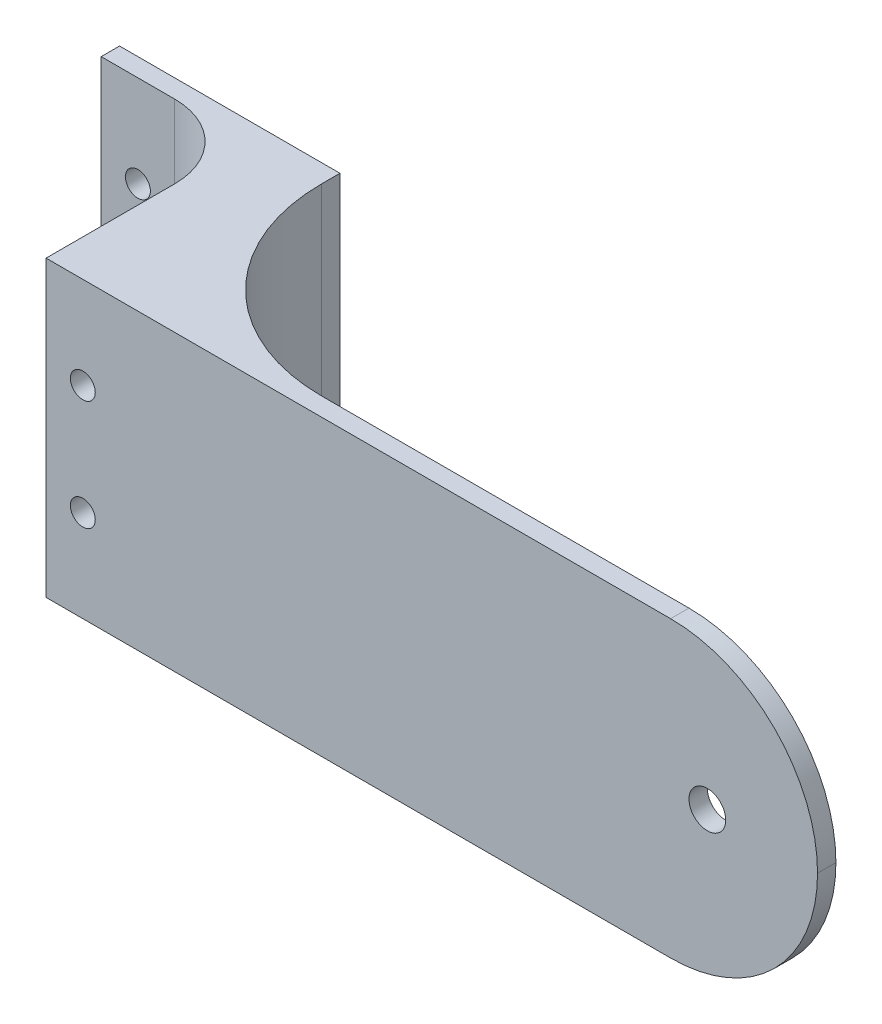
SolidWorks part; units mm, degrees
material "6061-T6 (SS)"
ref_plane "Front Plane" through (0, 0, 0) normal (0, 0, 1) x (1, 0, 0)
ref_plane "Top Plane" through (0, 0, 0) normal (0, 1, 0) x (1, 0, 0)
ref_plane "Right Plane" through (0, 0, 0) normal (1, 0, 0) x (0, 0, -1)
ref_plane "Plane1" through (0, 0, 15.875) normal (0, 0, 1) x (1, 0, 0)
sketch "Sketch1" plane through (0, 0, 15.875) normal (0, 0, 1) x (1, 0, 0)
  line L0 (0, -25.4) -> (0, 25.4) construction
  line L1 (0, 25.4) -> (-38.1, 25.4) construction
  line L2 (-38.1, 25.4) -> (-38.1, -25.4)
  line L3 (-38.1, -25.4) -> (-25.4, -25.4)
  line L5 (0, 25.4) -> (-38.1, 25.4)
  line L6 (-25.4, -25.4) -> (0, -25.4)
  line L7 (0, -25.4) -> (0, 25.4)
  point P2 (0, 0)
  dimension "D1" = 50.8
  dimension "D2" = 38.1
  dimension "D3" = 12.7
extrude "Boss-Extrude1" add sketch "Sketch1" along normal blind 3.175
ref_plane "Plane2" through (0, 0, 50.8) normal (0, 0, 1) x (1, 0, 0)
sketch "Sketch2" plane through (0, 0, 50.8) normal (0, 0, 1) x (1, 0, 0)
  line L0 (0, -25.4) -> (0, 25.4) construction
  line L1 (0, 25.4) -> (-12.7, 25.4)
  line L2 (-12.7, 25.4) -> (-12.7, -25.4)
  line L3 (-12.7, -25.4) -> (0, -25.4)
  line L4 (0, -25.4) -> (0, 25.4)
  point P2 (0, 0)
  dimension "D1" = 50.8
  dimension "D2" = 12.7
extrude "Boss-Extrude2" add sketch "Sketch2" against normal up to surface (31.75 mm away) up to face at (-19.05, 0, 19.05)
fillet "Fillet1" radius 12.7 1 edges at (-12.7, 0, 19.05)
sketch "Sketch3" plane through (0, 0, 50.8) normal (0, 0, 1) x (1, 0, 0)
  line L0 (0, 0) -> (0, 25.4) construction
  line L1 (0, -25.4) -> (0, 25.4) construction
  line L2 (0, 25.4) -> (101.6, 25.4)
  line L3 (101.6, 25.4) -> (120.65, 25.4)
  line L4 (120.65, 25.4) -> (120.65, -25.4)
  line L5 (120.65, -25.4) -> (0, -25.4)
  line L6 (0, -25.4) -> (-12.7, -25.4)
  line L7 (-12.7, -25.4) -> (-12.7, 25.4)
  line L8 (-12.7, 25.4) -> (0, 25.4)
  dimension "D1" = 19.05
  dimension "D2" = 101.6
  dimension "D3" = 50.8
  dimension "D4" = 12.7
extrude "Boss-Extrude3" add sketch "Sketch3" along normal blind 3.175
fillet "Fillet2" radius 31.75 1 edges at (0, 0, 50.8)
sketch "Sketch4" plane through (0, 0, 53.975) normal (0, 0, 1) x (1, 0, 0)
  line L0 (0, 0) -> (-55.8335, 0) construction
  line L1 (0, -25.4) -> (0, 25.4) construction
  line L2 (-38.1, 25.4) -> (-38.1, -25.4) construction
  line L3 (-38.1, 25.4) -> (-38.1, -25.4) construction
  line L6 (0, -25.4) -> (0, 25.4) construction
  line L8 (63.3409, -25.4) -> (63.3409, 25.4) construction
  circle A0 centre (-6.35, 9.525) radius 2.1527
  circle A2 centre (-31.75, 9.525) radius 2.1527
  circle A4 centre (-6.35, -9.525) radius 2.1527
  circle A5 centre (-31.75, -9.525) radius 2.1527
  dimension "D1" = 4.3053
  dimension "D2" = 6.35
  dimension "D3" = 9.525
  dimension "D4" = 19.05
  dimension "D5" = 25.4
  dimension "D6" = 38.1
extrude "Cut-Extrude1" cut sketch "Sketch4" against normal up to surface (38.1 mm away) up to face at (-19.05, 0, 15.875)
fillet "Fillet3" radius 25.4 2 edges at (120.65, -25.4, 52.3875) (120.65, 25.4, 52.3875)
sketch "Sketch5" plane through (0, 0, 53.975) normal (0, 0, 1) x (1, 0, 0)
  line L0 (63.3409, -25.4) -> (63.3409, 25.4) construction
  line L1 (63.3409, -25.4) -> (63.3409, 25.4) construction
  line L2 (95.25, 25.4) -> (-12.7, 25.4) construction
  line L3 (82.5851, -19.0149) -> (120.6149, 19.0149) construction
  line L4 (118.089, -16.489) -> (85.111, 16.489) construction
  line L5 (101.6, 0) -> (101.6, -34.636) construction
  circle A0 centre (101.6, 0) radius 3.175 construction
  circle A1 centre (101.6, 0) radius 9.525
  circle A2 centre (101.6, 0) radius 13 construction
  circle A4 centre (110.7924, 9.1924) radius 1.5875
  circle A5 centre (110.7924, -9.1924) radius 1.5875
  circle A6 centre (92.4076, -9.1924) radius 1.5875
  circle A7 centre (92.4076, 9.1924) radius 1.5875
  point P21 (101.6, 0)
  point P24 (101.6, 0)
  dimension "D2" = 6.35
  dimension "D3" = 19.05
  dimension "D4" = 26
  dimension "D5" = 3.175
  dimension "D6" = 25.4
  dimension "D7" = 45
  dimension "D8" = 90
extrude "Cut-Extrude2" [suppressed] cut sketch "Sketch5" against normal up to surface (3.175 mm away)
sketch "Sketch6" [suppressed] plane through (0, 0, 53.975) normal (0, 0, 1) x (1, 0, 0)
  line L0 (80.4908, -21.1092) -> (122.7092, 21.1092) construction
  line L1 (119.8449, -18.2449) -> (83.3551, 18.2449) construction
  line L2 (101.6, 0) -> (101.6, -31.1994) construction
  line L3 (95.25, 25.4) -> (-12.7, 25.4) construction
  circle A0 centre (101.6, 0) radius 8.55
  circle A1 centre (101.6, 0) radius 11 construction
  circle A2 centre (93.8218, 7.7782) radius 1.5875
  circle A3 centre (109.3782, 7.7782) radius 1.5875
  circle A4 centre (109.3782, -7.7782) radius 1.5875
  circle A5 centre (93.8218, -7.7782) radius 1.5875
  circle A6 centre (93.8218, 7.7782) radius 2.75 construction
  point P2 (0, 0)
  point P8 (101.6, 0)
  point P10 (101.6, 0)
  point P23 (95.7664, 5.8336)
  point P24 (95.5542, 6.0458)
  dimension "D2" = 17.1
  dimension "D3" = 22
  dimension "D6" = 3.175
  dimension "D8" = 5.5
  dimension "D1" = 101.6
  dimension "D4" = 45
  dimension "D5" = 45
  dimension "D7" = 25.4
extrude "Cut-Extrude3" [suppressed] cut sketch "Sketch6" against normal up to surface (3.175 mm away)
sketch "Sketch7" plane through (0, 0, 53.975) normal (0, 0, 1) x (1, 0, 0)
  line L0 (95.25, 25.4) -> (-12.7, 25.4) construction
  circle A0 centre (101.6, 0) radius 3.175
  point P2 (0, 0)
  dimension "D2" = 6.35
  dimension "D1" = 101.6
  dimension "D3" = 25.4
extrude "Cut-Extrude4" cut sketch "Sketch7" against normal up to next
